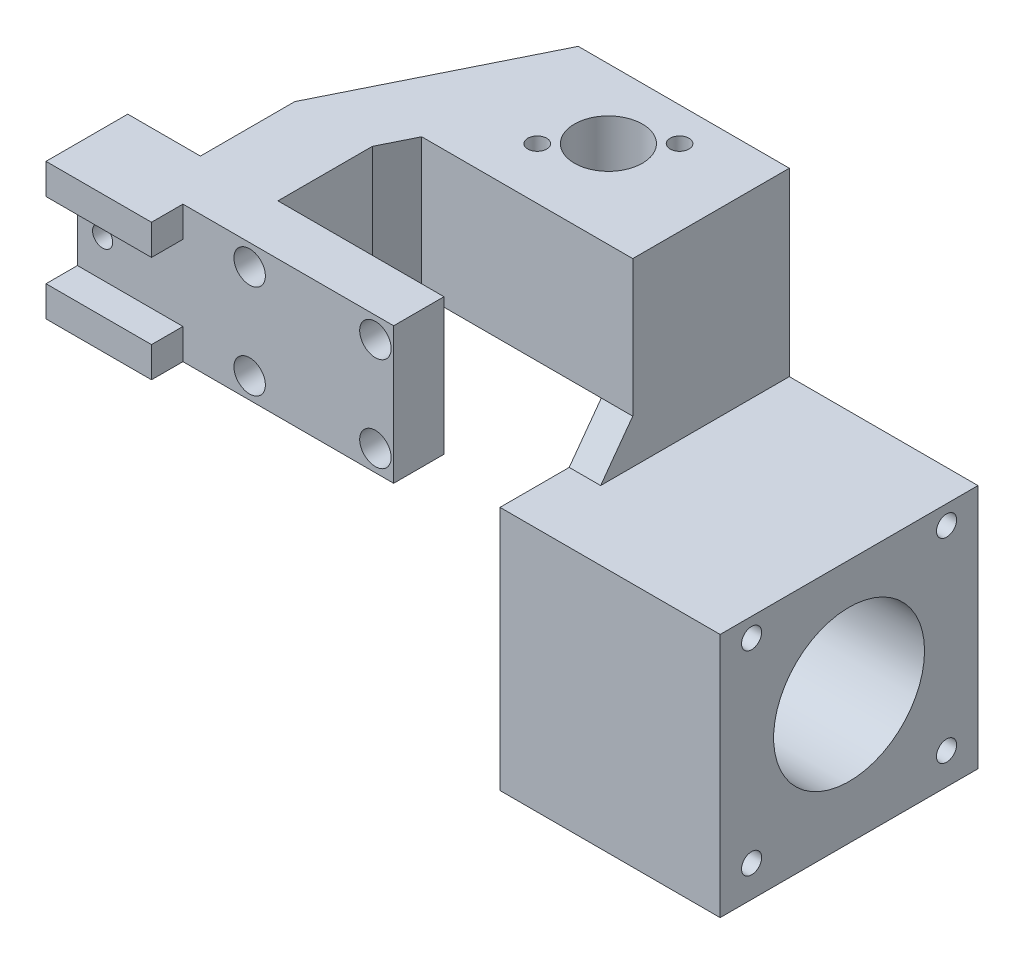
SolidWorks part; units mm, degrees
ref_plane "Přední rovina" through (0, 0, 0) normal (0, 0, 1) x (1, 0, 0)
ref_plane "Horní rovina" through (0, 0, 0) normal (0, 1, 0) x (1, 0, 0)
ref_plane "Pravá rovina" through (0, 0, 0) normal (1, 0, 0) x (0, 0, -1)
sketch "Skica1" plane through (0, 0, 0) normal (0, 0, 1) x (1, 0, 0)
  line L1 (16.212, -19.9414) -> (-34.0669, -19.9414)
  line L2 (16.212, -19.9414) -> (16.212, 1.7586)
  line L3 (16.212, 1.7586) -> (-34.0669, 1.7586)
  line L4 (-34.0669, -19.9414) -> (-34.0669, 1.7586)
  circle A0 centre (13.312, -16.5914) radius 1.6
  circle A1 centre (-6.688, -16.5914) radius 1.6
  circle A2 centre (-6.688, -1.5914) radius 1.6
  circle A3 centre (13.312, -1.5914) radius 1.6
  dimension "D1" = 3.2
  dimension "D2" = 2
  dimension "D3" = 2
extrude "Přidat vysunutím1" add sketch "Skica1" along normal blind 8
sketch "Skica2" plane through (0, 0, 8) normal (0, 0, 1) x (1, 0, 0)
  circle A0 centre (13.312, -16.5914) radius 2.5
  circle A1 centre (-6.688, -16.5914) radius 2.5
  circle A2 centre (-6.688, -1.5914) radius 2.5
  circle A3 centre (13.312, -1.5914) radius 2.5
  dimension "D1" = 5
  dimension "D2" = 2
  dimension "D3" = 2
extrude "Odebrat vysunutím1" cut sketch "Skica2" against normal blind 4
sketch "Skica3" plane through (0, 0, 8) normal (0, 0, 1) x (1, 0, 0)
  line L0 (-34.0669, 1.7586) -> (-34.0669, -19.9414) construction
  circle A0 centre (-30.0669, -9.0914) radius 1.6
  dimension "D1" = 3.2
  dimension "D2" = 4
extrude "Odebrat vysunutím2" cut sketch "Skica3" against normal blind 8
sketch "Skica4" plane through (0, 0, 0) normal (0, 0, -1) x (-1, 0, 0)
  line L0 (-16.212, 1.7586) -> (34.0669, 1.7586) construction
  line L1 (10.188, 1.7586) -> (22.5157, 1.7586)
  line L2 (10.188, 1.7586) -> (10.188, -19.9414)
  line L3 (10.188, -19.9414) -> (22.5157, -19.9414)
  line L4 (22.5157, 1.7586) -> (22.5157, -19.9414)
  line L5 (10.188, 1.7586) -> (10.188, -19.9414) construction
  line L6 (34.0669, -19.9414) -> (-16.212, -19.9414) construction
  line L7 (10.188, -19.9414) -> (10.188, 1.7586) construction
extrude "Přidat vysunutím2" add sketch "Skica4" along normal blind 15
sketch "Skica6" plane through (0, 1.7586, 0) normal (0, 1, 0) x (1, 0, 0)
  line L0 (-10.188, 15) -> (-22.5157, 15)
  line L1 (-10.188, 15) -> (-7.5858, 20.255)
  line L2 (-22.5157, 15) -> (-7.5858, 45.15)
  line L3 (4.7419, 45.15) -> (-7.5858, 45.15)
  line L5 (-7.5858, 45.15) -> (20.9737, 45.15)
  line L7 (-7.5858, 20.255) -> (20.9737, 20.255)
  line L8 (20.9737, 45.15) -> (20.9737, 20.255)
  circle A0 centre (8.2082, 34.15) radius 11 construction
  circle A3 centre (8.2082, 34.15) radius 5.4063
  line M11 (-10.188, 15) -> (-22.5157, 15)
extrude "Přidat vysunutím3" add sketch "Skica6" against normal up to surface (21.7 mm away) contours L8 L5 L3 L2 L1 L7 A3 M11 region at (1.476, 1.7586, -30.6172) up to face at (-12.6397, -19.9414, -1.75)
sketch "Skica7" plane through (0, -19.9414, 0) normal (0, -1, 0) x (1, 0, 0)
  line L0 (8.2082, -34.15) -> (0.2082, -34.15) construction
  line L1 (8.2082, -34.15) -> (2.5514, -28.4931) construction
  line L2 (8.2082, -34.15) -> (13.8651, -39.8069) construction
  circle A0 centre (8.2082, -34.15) radius 8 construction
  circle A1 centre (2.5514, -28.4931) radius 1.5
  circle A2 centre (13.8651, -39.8069) radius 1.5
  point P12 (8.2082, -34.15)
  dimension "D1" = 16
  dimension "D2" = 3
  dimension "D3" = 2
extrude "Odebrat vysunutím3" cut sketch "Skica7" against normal up to surface (21.7 mm away) up to face at (-6.1951, 1.7586, -12.0675)
sketch "Skica9" plane through (20.9737, 0, 0) normal (1, 0, 0) x (0, 0, -1)
  line L0 (20.255, -19.9414) -> (15, -19.9414) construction
  line L1 (40.15, -29.9414) -> (9.15, -29.9414) construction
  line L2 (40.15, -29.9414) -> (40.15, -60.9414) construction
  line L3 (40.15, -60.9414) -> (9.15, -60.9414) construction
  line L4 (9.15, -29.9414) -> (9.15, -60.9414) construction
  line L5 (45.15, 1.7586) -> (20.255, 1.7586)
  line L6 (45.15, 1.7586) -> (45.15, -19.9414)
  line L8 (20.255, 1.7586) -> (20.255, -19.9414)
  line L10 (45.15, -19.9414) -> (45.15, -65.9414)
  line L11 (45.15, -65.9414) -> (15.15, -65.9414)
  line L13 (15.15, -60.9414) -> (15.15, -65.9414)
  line L14 (15.15, -65.9414) -> (4.15, -65.9414)
  line L15 (15.15, -65.9414) -> (15.15, -60.9414)
  line L16 (15.15, -26.9414) -> (4.15, -26.9414)
  line L17 (4.15, -65.9414) -> (4.15, -26.9414)
  line L19 (15.15, -26.9414) -> (20.255, -19.9414)
  line L20 (24.65, -45.4414) -> (9.15, -45.4414) construction
  line L21 (24.65, -45.4414) -> (24.65, -60.9414) construction
  circle A0 centre (40.15, -60.9414) radius 1.6
  circle A1 centre (9.15, -60.9414) radius 1.6
  circle A2 centre (9.15, -29.9414) radius 1.6
  circle A3 centre (40.15, -29.9414) radius 1.6
  circle A4 centre (24.65, -45.4414) radius 12
  line M15 (20.255, 1.7586) -> (20.255, -19.9414)
  line M16 (20.255, -19.9414) -> (45.15, -19.9414)
  line M17 (45.15, -19.9414) -> (45.15, 1.7586)
  line M18 (45.15, 1.7586) -> (20.255, 1.7586)
  dimension "D2" = 3.2
  dimension "D8" = 24
  dimension "D1" = 31
  dimension "D5" = 10
  dimension "D6" = 5
  dimension "D7" = 5
  dimension "D9" = 5
  dimension "D10" = 3
  dimension "D3" = 2
  dimension "D4" = 2
extrude "Přidat vysunutím4" add sketch "Skica9" along normal blind 5 contours M18 M15 M16 M17 | L19 L16 L17 L14 L11 L10 A3 A2 A1 A0 M16 region at (20.9737, -9.0914, -32.7025) region at (20.9737, -42.9414, -44.5338)
sketch "Skica10" plane through (25.9737, 0, 0) normal (1, 0, 0) x (0, 0, -1)
  line L1 (4.15, -26.9414) -> (45.15, -26.9414)
  line L2 (4.15, -26.9414) -> (4.15, -65.9414)
  line L3 (4.15, -65.9414) -> (45.15, -65.9414)
  line L4 (45.15, -26.9414) -> (45.15, -65.9414)
  circle A0 centre (24.65, -45.4414) radius 12 construction
  circle A1 centre (40.15, -60.9414) radius 1.6 construction
  circle A2 centre (40.15, -29.9414) radius 1.6 construction
  circle A3 centre (9.15, -29.9414) radius 1.6 construction
  circle A4 centre (9.15, -60.9414) radius 1.6 construction
  circle A5 centre (24.65, -45.4414) radius 12
  circle A6 centre (40.15, -60.9414) radius 1.6
  circle A7 centre (40.15, -29.9414) radius 1.6
  circle A8 centre (9.15, -29.9414) radius 1.6
  circle A9 centre (9.15, -60.9414) radius 1.6
extrude "Přidat vysunutím5" add sketch "Skica10" along normal blind 30
sketch "Skica11" plane through (0, 0, 8) normal (0, 0, 1) x (1, 0, 0)
  line L0 (-34.0669, -19.9414) -> (16.212, -19.9414) construction
  line L1 (-34.0669, -15.0914) -> (-17.293, -15.0914)
  line L3 (-34.0669, -3.0914) -> (-17.293, -3.0914)
  line L7 (-34.0669, 1.7586) -> (-17.293, 1.7586)
  line L8 (-34.0669, 1.7586) -> (-34.0669, -3.0914)
  line L9 (-34.0669, -19.9414) -> (-17.293, -19.9414)
  line L10 (-17.293, 1.7586) -> (-17.293, -3.0914)
  line L11 (-17.293, -15.0914) -> (-17.293, -19.9414)
  line L13 (-34.0669, -15.0914) -> (-34.0669, -19.9414)
  point P0 (-30.0669, -9.0914)
  dimension "D1" = 12
extrude "Přidat vysunutím6" add sketch "Skica11" along normal blind 5
